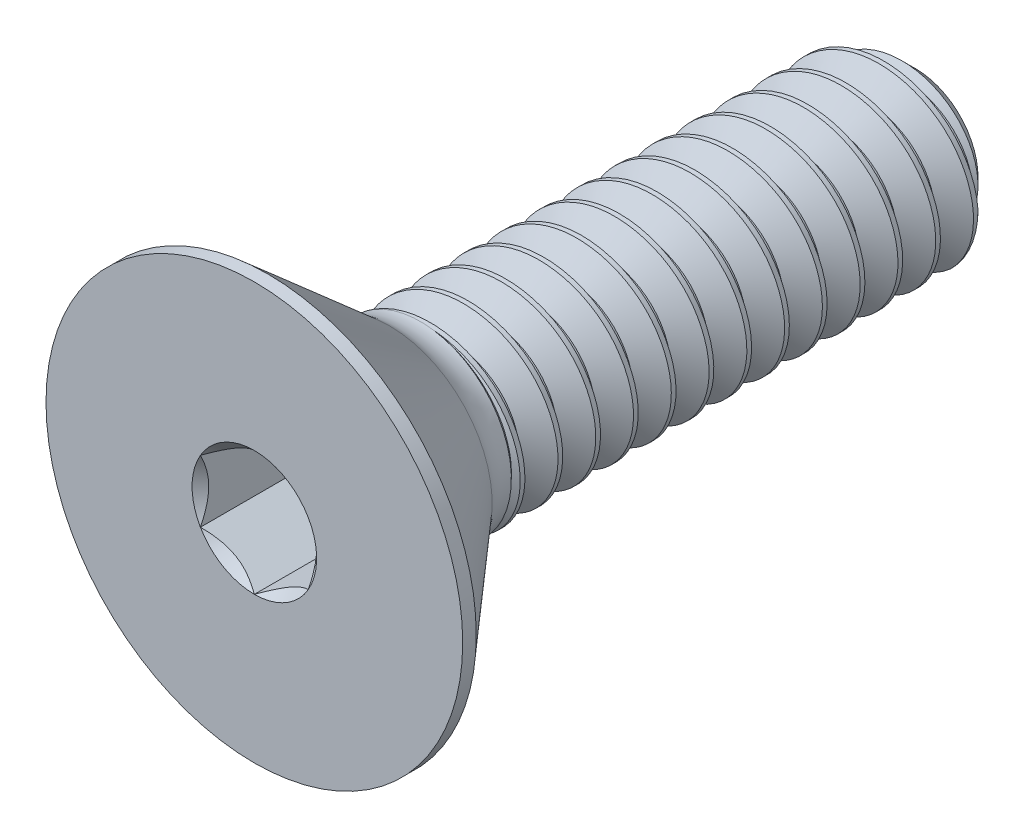
SolidWorks part; units mm, degrees
ref_plane "Front" through (0, 0, 0) normal (0, 0, 1) x (1, 0, 0)
ref_plane "Top" through (0, 0, 0) normal (0, 1, 0) x (1, 0, 0)
ref_plane "Right" through (0, 0, 0) normal (1, 0, 0) x (0, 0, -1)
sketch "Sketch1" plane through (0, 0, 0) normal (1, 0, 0) x (0, 0, -1)
  line L0 (0, 2.5019) -> (0.1626, 2.5019) construction
  line L1 (0.1626, 2.5019) -> (1.6256, 1.2301) construction
  line L2 (0, 1.0922) -> (7.9375, 1.0922)
  line L3 (7.9375, 1.0922) -> (7.9375, 0)
  line L4 (7.9375, 0) -> (0, 0)
  line L5 (0, 0) -> (0, 2.5019) construction
  line L6 (0, 2.5019) -> (0, -2.5019) construction
  line L7 (7.9375, 1.0922) -> (7.9375, -1.0922) construction
  line L8 (0, -2.5019) -> (0.1626, -2.5019) construction
  line L9 (0.1626, -2.5019) -> (1.6256, -1.2301) construction
  line L11 (0, 1.0922) -> (0, 0)
  line L12 (1.9944, 1.0922) -> (1.9944, 0) construction
  arc A1 (1.6256, 1.2301) -> (1.9944, 1.0922) centre (1.9944, 1.6544) ccw construction
  dimension "D1" = 0.1626
revolve "Revolve1" add sketch "Sketch1" angle 360 mid plane about L4
sketch "Sketch3" plane through (0, 0, -7.9375) normal (0, 0, -1) x (-1, 0, 0)
  circle A0 centre (0, 0) radius 1.0922
curve "Helix/Spiral1" pitch 0.4536 height 7.9375 radius 1.0922 centre (0, 0, -7.9375) axis (0, 0, 1) start towards (0, 1, 0)
sketch "Sketch2" plane through (0, 0, 0) normal (1, 0, 0) x (0, 0, -1)
  line L0 (7.9375, 1.0922) -> (8.3344, 1.0922)
  line L1 (8.3344, 1.0922) -> (8.1643, 0.7976)
  line L2 (8.1643, 0.7976) -> (8.1076, 0.7976)
  line L3 (8.1076, 0.7976) -> (7.9375, 1.0922)
  line L4 (8.0225, 0.9449) -> (8.2493, 0.9449) construction
  dimension "D1" = 60
  dimension "D2" = 0.0567
  dimension "D3" = 0.2268
chamfer "Chamfer1" distance 0.3402 angle 45 1 edges at (0, 1.0922, -7.9375)
sweep "Cut-Sweep1" cut profiles "Sketch2" path "Helix/Spiral1" align with end faces yes
sketch "Sketch7" plane through (0, 0, 0) normal (1, 0, 0) x (0, 0, -1)
  line L0 (0, 2.5019) -> (0.1626, 2.5019) construction
  line L1 (0.1626, 2.5019) -> (1.6256, 1.2301) construction
  line L2 (0, 2.5019) -> (0.1626, 2.5019)
  line L3 (0.1626, 2.5019) -> (1.6256, 1.2301)
  line L4 (1.9944, 1.0922) -> (1.9944, 0) construction
  line L5 (1.9944, 1.0922) -> (1.9944, 0)
  line L7 (0, 0) -> (0, 2.5019) construction
  line L8 (0, 0) -> (0, 2.5019)
  line L9 (0, 0) -> (1.9944, 0)
  line L10 (2.7521, 0) -> (-2.7521, 0) construction
  arc A0 (1.6256, 1.2301) -> (1.9944, 1.0922) centre (1.9944, 1.6544) ccw construction
  arc A1 (1.6256, 1.2301) -> (1.9944, 1.0922) centre (1.9944, 1.6544) ccw
revolve "Revolve2" add sketch "Sketch7" angle 360 mid plane about L9
ref_plane "Plane1" through (0, 0, -1.9944) normal (0, 0, 1) x (1, 0, 0)
sketch "Sketch8" plane through (0, 0, -1.9944) normal (0, 0, 1) x (1, 0, 0)
  circle A0 centre (0, 0) radius 1.0922
extrude "Boss-Extrude1" add sketch "Sketch8" against normal through all draft 45
sketch "Sketch5" plane through (0, 0, 0) normal (0, 0, 1) x (1, 0, 0)
  line L1 (0.6477, -0.3739) -> (0.6477, 0.3739)
  line L2 (0.6477, 0.3739) -> (0, 0.7479)
  line L3 (0, 0.7479) -> (-0.6477, 0.3739)
  line L4 (-0.6477, 0.3739) -> (-0.6477, -0.3739)
  line L5 (-0.6477, -0.3739) -> (0, -0.7479)
  line L6 (0, -0.7479) -> (0.6477, -0.3739)
  circle A0 centre (0, 0) radius 0.6477 construction
  dimension "Hex" = 1.2954
extrude "Cut-Extrude2" cut sketch "Sketch5" against normal blind 1.1379
sketch "Sketch6" plane through (0, 0, 0) normal (0, 0, 1) x (1, 0, 0)
  circle A0 centre (0, 0) radius 0.7479
extrude "Cut-Extrude3" cut sketch "Sketch6" against normal blind 1.1379 draft 45
sketch "Sketch9" [suppressed] plane through (0, 0, -1.9944) normal (0, 0, 1) x (1, 0, 0)
  circle A1 centre (0, 0) radius 1.0922
  circle A2 centre (0, 0) radius 1.0922
  point P0 (0, 1.0922)
  dimension "D1" = 0
extrude "Boss-Extrude2" [suppressed] add sketch "Sketch9" against normal offset from surface (1.1806 mm away) 22.225 up to face at (0, 0.752, -7.9375)
sketch "Sketch10" plane through (0, 0, 0) normal (1, 0, 0) x (0, 0, -1)
  line L0 (7.9375, 1.0922) -> (7.9375, -1.0922) construction
  point P0 (7.2571, -1.0922)
  dimension "D1" = 0.6804
equation "\"D3@Helix/Spiral1\" = \"Lg@Sketch1\""
equation "\"D2@Sketch2\" = \"D4@Helix/Spiral1\" * .125"
equation "\"D3@Sketch2\" = \"D4@Helix/Spiral1\" * .5"
equation "\"D1@Chamfer1\" = \"D4@Helix/Spiral1\" * .75"
equation "\"D1@Cut-Extrude2\" = \"Head Ht@Sketch1\" * .7"
equation "\"D1@Sketch1\" = \"Head Ht@Sketch1\" * .1"
equation "\"D1@Sketch10\" = \"D4@Helix/Spiral1\" * 1.5"
equation "\"D1@Cut-Extrude3\" = \"D1@Cut-Extrude2\""
